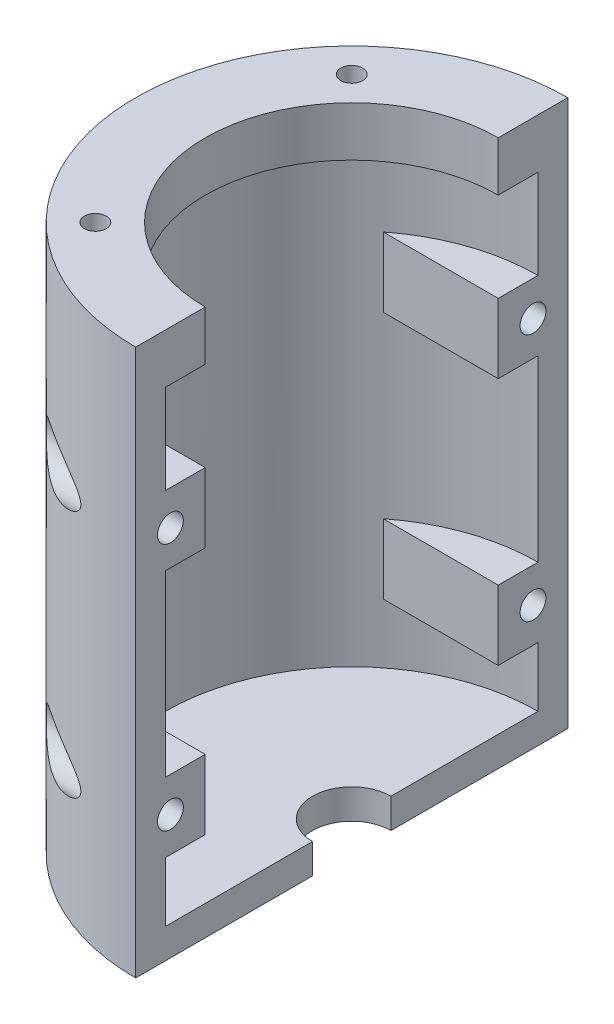
SolidWorks part; units mm, degrees
ref_plane "正面" through (0, 0, 0) normal (0, 0, 1) x (1, 0, 0)
ref_plane "平面" through (0, 0, 0) normal (0, 1, 0) x (1, 0, 0)
ref_plane "右側面" through (0, 0, 0) normal (1, 0, 0) x (0, 0, -1)
sketch "ｽｹｯﾁ1" plane through (0, 0, 0) normal (0, 1, 0) x (1, 0, 0)
  line L0 (0, -21.75) -> (0, -14.75)
  line L1 (0, -14.75) -> (0, 14.75) construction
  line L2 (0, 14.75) -> (0, 21.75)
  arc A0 (0, 21.75) -> (0, -21.75) centre (0, 0) ccw
  arc A1 (0, 14.75) -> (0, -14.75) centre (0, 0) ccw
  dimension "D1" = 14.75
  dimension "D2" = 7
extrude "ﾎﾞｽ - 押し出し1" add sketch "ｽｹｯﾁ1" along normal blind 55
sketch "ｽｹｯﾁ2" plane through (0, 55, 0) normal (0, 1, 0) x (1, 0, 0)
  circle A0 centre (0, 0) radius 14.75
  circle A1 centre (0, 0) radius 18.75
  arc A2 (0, 14.75) -> (0, -14.75) centre (0, 0) ccw construction
  arc A3 (0, 21.75) -> (0, -21.75) centre (0, 0) ccw construction
  dimension "D1" = 3
extrude "ｶｯﾄ - 押し出し1" cut sketch "ｽｹｯﾁ2" against normal through all from offset 5 offset against normal yes
sketch "ｽｹｯﾁ4" plane through (0, 0, 0) normal (1, 0, 0) x (0, 0, -1)
  line L0 (-14.75, 12.5) -> (-21.75, 12.5) construction
  line L1 (-21.75, 41) -> (-21.75, 34)
  line L2 (-18.75, 50) -> (-14.75, 50) construction
  line L3 (21.75, 55) -> (21.75, 0) construction
  line L4 (18.75, 50) -> (18.75, 0) construction
  line L5 (-21.75, 16) -> (-14.75, 16)
  line L6 (-14.75, 16) -> (-14.75, 9)
  line L7 (-14.75, 9) -> (-21.75, 9)
  line L8 (-21.75, 9) -> (-21.75, 16)
  line L9 (-21.75, 50) -> (21.75, 50) construction
  line L10 (0, 25) -> (-21.75, 25) construction
  line L11 (0, 25) -> (21.75, 25) construction
  line L12 (-21.75, 37.5) -> (21.75, 37.5) construction
  line L13 (-21.75, 0) -> (21.75, 0) construction
  line L14 (0, 50) -> (0, 0) construction
  line L15 (-18.25, 50) -> (-18.25, 0) construction
  line L16 (18.75, 50) -> (18.75, 37.5) construction
  line L17 (18.75, 37.5) -> (18.75, 25) construction
  line L18 (-21.75, 55) -> (-21.75, 0) construction
  line L19 (-21.75, 34) -> (-14.75, 34)
  line L20 (-14.75, 34) -> (-14.75, 41)
  line L21 (-14.75, 41) -> (-21.75, 41)
  line L22 (21.75, 9) -> (21.75, 16)
  line L23 (21.75, 16) -> (14.75, 16)
  line L24 (14.75, 16) -> (14.75, 9)
  line L25 (14.75, 9) -> (21.75, 9)
  line L26 (21.75, 34) -> (14.75, 34)
  line L27 (21.75, 41) -> (21.75, 34)
  line L28 (14.75, 41) -> (21.75, 41)
  line L29 (14.75, 34) -> (14.75, 41)
  circle A0 centre (-18.25, 37.5) radius 1.1 construction
  circle A1 centre (18.25, 37.5) radius 1.1 construction
  circle A2 centre (18.25, 12.5) radius 1.1 construction
  circle A3 centre (-18.25, 12.5) radius 1.1 construction
  dimension "D1" = 2.2
  dimension "D2" = 3.5
  dimension "D3" = 7
  dimension "D4" = 7
extrude "ﾎﾞｽ - 押し出し3" add sketch "ｽｹｯﾁ4" against normal up to next
sketch "ｽｹｯﾁ3" plane through (0, 0, 0) normal (1, 0, 0) x (0, 0, -1)
  line L0 (-21.75, 50) -> (21.75, 50) construction
  line L1 (0, 25) -> (-21.75, 25) construction
  line L2 (0, 25) -> (21.75, 25) construction
  line L3 (-21.75, 55) -> (-21.75, 0) construction
  line L4 (-21.75, 37.5) -> (21.75, 37.5) construction
  line L5 (21.75, 55) -> (21.75, 0) construction
  line L6 (-21.75, 0) -> (21.75, 0) construction
  line L7 (0, 50) -> (0, 0) construction
  line L8 (14.75, 50) -> (18.75, 50) construction
  line L9 (-18.25, 50) -> (-18.25, 0) construction
  line L10 (18.75, 50) -> (18.75, 37.5) construction
  line L11 (18.75, 37.5) -> (18.75, 25) construction
  line L12 (18.75, 50) -> (18.75, 41) construction
  circle A0 centre (-18.25, 37.5) radius 1.3
  circle A1 centre (18.25, 37.5) radius 1.3
  circle A2 centre (18.25, 12.5) radius 1.3
  circle A3 centre (-18.25, 12.5) radius 1.3
  dimension "D1" = 2.6
  dimension "D2" = 3.5
extrude "ｶｯﾄ - 押し出し2" cut sketch "ｽｹｯﾁ3" against normal blind 5
sketch "ｽｹｯﾁ5" plane through (0, 0, 0) normal (1, 0, 0) x (0, 0, -1)
  circle A0 centre (-18.25, 37.5) radius 2.5
  circle A1 centre (-18.25, 12.5) radius 2.5
  circle A2 centre (18.25, 12.5) radius 2.5
  circle A3 centre (18.25, 37.5) radius 2.5
  dimension "D1" = 5
extrude "ｶｯﾄ - 押し出し3" cut sketch "ｽｹｯﾁ5" against normal through all from offset 4 offset against normal yes
sketch "ｽｹｯﾁ6" plane through (0, 55, 0) normal (0, 1, 0) x (1, 0, 0)
  line L0 (0, 0) -> (-14.75, 0) construction
  line L1 (-14.75, 0) -> (-18.25, 0) construction
  line L2 (-18.25, 0) -> (-21.75, 0) construction
  line L3 (0, 0) -> (-12.9047, -12.9047) construction
  line L4 (-12.9047, 12.9047) -> (0, 0) construction
  circle A0 centre (0, 0) radius 18.25 construction
  arc A1 (0, 14.75) -> (0, -14.75) centre (0, 0) ccw construction
  arc A2 (0, 21.75) -> (0, -21.75) centre (0, 0) ccw construction
  circle A3 centre (-12.9047, -12.9047) radius 1.1
  circle A4 centre (-12.9047, 12.9047) radius 1.1
  dimension "D2" = 2.2
  dimension "D1" = 45
  dimension "D4" = 90
  dimension "D3" = 2
extrude "ｶｯﾄ - 押し出し4" cut sketch "ｽｹｯﾁ6" against normal up to vertex (5 mm away) up to point (0, 50, -14.75)
sketch "ｽｹｯﾁ7" plane through (0, 0, 0) normal (0, -1, 0) x (1, 0, 0)
  line L0 (0, -18.75) -> (0, -21.75) construction
  line L1 (0, -18.75) -> (0, 18.75) construction
  line L2 (0, -3.95) -> (0, -18.75)
  line L3 (0, 3.95) -> (0, 18.75)
  arc A0 (0, 18.75) -> (0, -18.75) centre (0, 0) ccw
  arc A1 (0, 3.95) -> (0, -3.95) centre (0, 0) ccw
  dimension "D1" = 3.95
extrude "ﾎﾞｽ - 押し出し4" add sketch "ｽｹｯﾁ7" against normal blind 3
